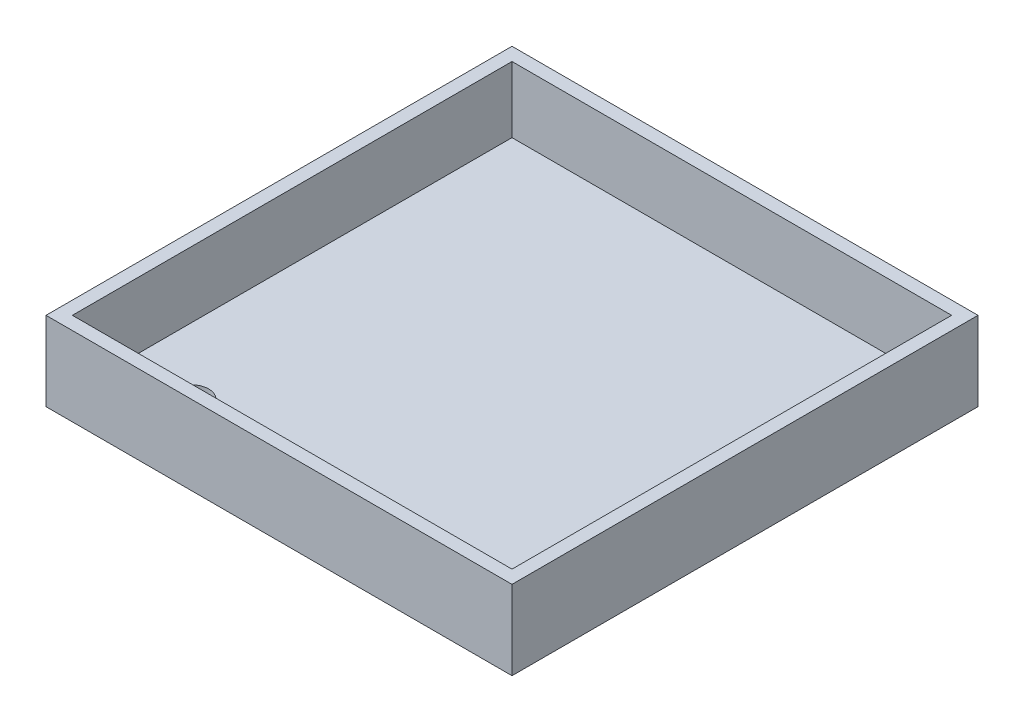
SolidWorks part; units mm, degrees
ref_plane "Front Plane" through (0, 0, 0) normal (0, 0, 1) x (1, 0, 0)
ref_plane "Top Plane" through (0, 0, 0) normal (0, 1, 0) x (1, 0, 0)
ref_plane "Right Plane" through (0, 0, 0) normal (1, 0, 0) x (0, 0, -1)
sketch "Sketch3" plane through (0, 0, 0) normal (0, 1, 0) x (1, 0, 0)
  line L1 (0, 0) -> (100, 0)
  line L2 (0, 0) -> (0, -100)
  line L3 (0, -100) -> (100, -100)
  line L4 (100, 0) -> (100, -100)
  dimension "D1" = 100
extrude "Boss-Extrude1" add sketch "Sketch3" along normal blind 3
sketch "Sketch5" plane through (0, 0, 100) normal (0, 0, 1) x (1, 0, 0)
  line L0 (100, 3) -> (100, 0) construction
  line L1 (0, 0) -> (100, 0)
  line L2 (0, 0) -> (0, 18)
  line L3 (0, 18) -> (100, 18)
  line L4 (100, 0) -> (100, 18)
  point P5 (100, 9)
  dimension "D1" = 18
extrude "Boss-Extrude2" add sketch "Sketch5" along normal blind 3
sketch "Sketch6" plane through (0, 0, 0) normal (0, 0, -1) x (-1, 0, 0)
  line L1 (-100, 0) -> (0, 0)
  line L2 (-100, 0) -> (-100, 18)
  line L3 (-100, 18) -> (0, 18)
  line L4 (0, 0) -> (0, 18)
extrude "Boss-Extrude3" add sketch "Sketch6" along normal blind 3
sketch "Sketch7" plane through (0, 0, 0) normal (-1, 0, 0) x (0, 0, 1)
  line L1 (-3, 0) -> (103, 0)
  line L2 (-3, 0) -> (-3, 18)
  line L3 (-3, 18) -> (103, 18)
  line L4 (103, 0) -> (103, 18)
extrude "Boss-Extrude4" add sketch "Sketch7" along normal blind 3
sketch "Sketch9" plane through (100, 0, 0) normal (1, 0, 0) x (0, 0, -1)
  line L1 (-103, 0) -> (3, 0)
  line L2 (-103, 0) -> (-103, 18)
  line L3 (-103, 18) -> (3, 18)
  line L4 (3, 0) -> (3, 18)
extrude "Boss-Extrude5" add sketch "Sketch9" along normal blind 3
hole_wizard "Ø8.0mm Dowel Hole1" positions "Sketch10" profile "Sketch11" hole size "Ø8.0" standard "AS" end condition through all
sketch "Sketch10" plane through (0, 3, 0) normal (0, 1, 0) x (1, 0, 0)
  line L0 (103, -103) -> (-3, -103) construction
  line L1 (-3, -103) -> (-3, 3) construction
  point P0 (15, -88)
  dimension "D1" = 15
  dimension "D2" = 18
sketch "Sketch11" plane through (15, 3, 88) normal (1, 0, 0) x (0, 0, 1)
  line L0 (0, 0) -> (0, 3)
  line L1 (0, 3) -> (4, 3)
  line L2 (4, 3) -> (4, 0)
  line L5 (4, 0) -> (0, 0)
  line L11 (0, -6.35) -> (0, 107.95) construction
  dimension "Thru Hole Dia." = 8
  dimension "Thru Hole Depth" = 3
hole_wizard "Ø4.0mm Dowel Hole1" positions "Sketch12" profile "Sketch13" hole size "Ø4.0" standard "AS" end condition through all
sketch "Sketch12" plane through (0, 3, 0) normal (0, 1, 0) x (1, 0, 0)
  line L1 (89, -88) -> (15, -88) construction
  circle A0 centre (15, -88) radius 4 construction
  point P0 (89, -88)
  dimension "D1" = 74
sketch "Sketch13" plane through (89, 3, 88) normal (1, 0, 0) x (0, 0, 1)
  line L0 (0, 0) -> (0, 3)
  line L1 (0, 3) -> (2, 3)
  line L2 (2, 3) -> (2, 0)
  line L5 (2, 0) -> (0, 0)
  line L11 (0, -6.35) -> (0, 107.95) construction
  dimension "Thru Hole Dia." = 4
  dimension "Thru Hole Depth" = 3
sketch "Sketch15" plane through (0, 0, 0) normal (0, -1, 0) x (-1, 0, 0)
  line L0 (-50, -103) -> (-50, 3) construction
  line L1 (3, -103) -> (-103, -103) construction
  line L2 (-103, 3) -> (3, 3) construction
  point P6 (-50, -50)
ref_axis "Axis1" through (50, 0, 50) along (0, 1, 0)
